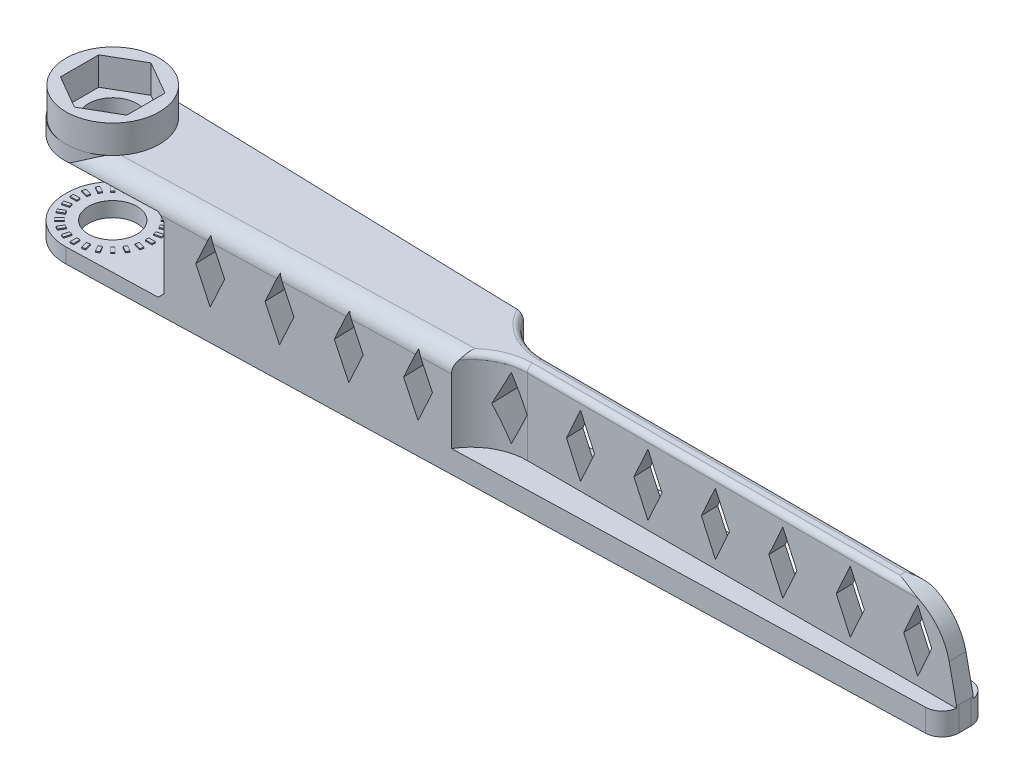
SolidWorks part; units mm, degrees
ref_plane "Front Plane" through (0, 0, 0) normal (0, 0, 1) x (1, 0, 0)
ref_plane "Top Plane" through (0, 0, 0) normal (0, 1, 0) x (1, 0, 0)
ref_plane "Right Plane" through (0, 0, 0) normal (1, 0, 0) x (0, 0, -1)
sketch "Sketch1" plane through (0, 0, 0) normal (0, 1, 0) x (1, 0, 0)
  line L0 (0, 8.2282) -> (0, 8.7718)
  line L1 (8.2249, 16.7687) -> (157.0843, 12.582)
  line L2 (160, 9.5832) -> (160, 7.4168)
  line L3 (157.0843, 4.418) -> (8.2249, 0.2313)
  line L4 (160, 8.5) -> (0, 8.5) construction
  arc A0 (160, 7.4168) -> (157.0843, 4.418) centre (157, 7.4168) cw
  arc A1 (157.0843, 12.582) -> (160, 9.5832) centre (157, 9.5832) cw
  arc A2 (8.2249, 0.2313) -> (0, 8.2282) centre (8, 8.2282) cw
  arc A3 (0, 8.7718) -> (8.2249, 16.7687) centre (8, 8.7718) cw
  point P7 (24.5016, 9.4444)
  point P8 (0, 8.5)
  point P9 (116.4876, 4.1839)
  point P12 (160, 4.5)
  point P15 (160, 12.5)
  point P18 (0, 0)
  point P21 (0, 17)
  dimension "D4" = 3
  dimension "D5" = 8
  dimension "D1" = 17
  dimension "D2" = 8
  dimension "D3" = 160
extrude "Boss-Extrude1" add sketch "Sketch1" along normal blind 18.5
sketch "Sketch2" plane through (0, 18.5, 0) normal (0, 1, 0) x (1, 0, 0)
  line L0 (75, 14.8906) -> (75, 10)
  line L1 (75, 7) -> (157, 7)
  line L2 (157, 7) -> (157, 10)
  line L3 (157, 10) -> (75, 10)
  line L4 (160, 7.4168) -> (160, 9.5832)
  line L5 (157.0843, 12.582) -> (8.2249, 16.7687)
  line L6 (0, 8.7718) -> (0, 8.2282)
  line L7 (8.2249, 0.2313) -> (157.0843, 4.418)
  line L8 (160, 7.4168) -> (160, 9.5832)
  line L9 (157.0843, 12.582) -> (75, 14.8906)
  line L11 (75, 2.1094) -> (157.0843, 4.418)
  line L12 (160, 8.5) -> (157, 8.5) construction
  line L15 (75, 7) -> (75, 2.1094)
  arc A4 (157.0843, 4.418) -> (160, 7.4168) centre (157, 7.4168) ccw
  arc A5 (160, 9.5832) -> (157.0843, 12.582) centre (157, 9.5832) ccw
  arc A6 (8.2249, 16.7687) -> (0, 8.7718) centre (8, 8.7718) ccw
  arc A7 (0, 8.2282) -> (8.2249, 0.2313) centre (8, 8.2282) ccw
  arc A8 (157.0843, 4.418) -> (160, 7.4168) centre (157, 7.4168) ccw
  arc A9 (160, 9.5832) -> (157.0843, 12.582) centre (157, 9.5832) ccw
  point P13 (0, 0)
  point P16 (75, 9.5832)
  dimension "D2" = 75
  dimension "D3" = 3
  dimension "D4" = 3
  dimension "D1" = 0
extrude "Cut-Extrude1" cut sketch "Sketch2" against normal offset from surface (14.5 mm away) 4 up to face at (81.0572, 0, -8.5)
chamfer "Chamfer1" distance 14.5 angle 12 1 edges at (157, 4, -8.5)
sketch "Sketch3" plane through (0, 0, 0) normal (0.0281, 0, 0.9996) x (0.9996, 0, -0.0281)
  line L0 (30.7282, 11) -> (33.2282, 16.5)
  line L1 (33.2282, 16.5) -> (35.7282, 11)
  line L2 (35.7282, 11) -> (33.2282, 5.5)
  line L3 (33.2282, 5.5) -> (30.7282, 11)
  line L4 (33.2282, 16.5) -> (33.2282, 5.5) construction
  line L5 (30.7282, 11) -> (35.7282, 11) construction
  line L6 (8.2282, 11) -> (33.2282, 11) construction
  line L7 (8.2282, 18.5) -> (8.2282, 0) construction
  line L8 (42.7282, 11) -> (45.2282, 16.5)
  line L9 (45.2282, 16.5) -> (47.7282, 11)
  line L10 (47.7282, 11) -> (45.2282, 5.5)
  line L11 (45.2282, 5.5) -> (42.7282, 11)
  line L12 (45.2282, 16.5) -> (45.2282, 5.5) construction
  line L13 (42.7282, 11) -> (47.7282, 11) construction
  line L14 (20.2282, 11) -> (45.2282, 11) construction
  line L15 (54.7282, 11) -> (57.2282, 16.5)
  line L16 (57.2282, 16.5) -> (59.7282, 11)
  line L17 (59.7282, 11) -> (57.2282, 5.5)
  line L18 (57.2282, 5.5) -> (54.7282, 11)
  line L19 (57.2282, 16.5) -> (57.2282, 5.5) construction
  line L20 (54.7282, 11) -> (59.7282, 11) construction
  line L21 (32.2282, 11) -> (57.2282, 11) construction
  line L22 (66.7282, 11) -> (69.2282, 16.5)
  line L23 (69.2282, 16.5) -> (71.7282, 11)
  line L24 (71.7282, 11) -> (69.2282, 5.5)
  line L25 (69.2282, 5.5) -> (66.7282, 11)
  line L26 (69.2282, 16.5) -> (69.2282, 5.5) construction
  line L27 (66.7282, 11) -> (71.7282, 11) construction
  line L28 (44.2282, 11) -> (69.2282, 11) construction
  line L29 (78.7282, 11) -> (81.2282, 16.5)
  line L30 (81.2282, 16.5) -> (83.7282, 11)
  line L31 (83.7282, 11) -> (81.2282, 5.5)
  line L32 (81.2282, 5.5) -> (78.7282, 11)
  line L33 (81.2282, 16.5) -> (81.2282, 5.5) construction
  line L34 (78.7282, 11) -> (83.7282, 11) construction
  line L35 (56.2282, 11) -> (81.2282, 11) construction
  line L36 (90.7282, 11) -> (93.2282, 16.5)
  line L37 (93.2282, 16.5) -> (95.7282, 11)
  line L38 (95.7282, 11) -> (93.2282, 5.5)
  line L39 (93.2282, 5.5) -> (90.7282, 11)
  line L40 (93.2282, 16.5) -> (93.2282, 5.5) construction
  line L41 (90.7282, 11) -> (95.7282, 11) construction
  line L42 (68.2282, 11) -> (93.2282, 11) construction
  line L43 (102.7282, 11) -> (105.2282, 16.5)
  line L44 (105.2282, 16.5) -> (107.7282, 11)
  line L45 (107.7282, 11) -> (105.2282, 5.5)
  line L46 (105.2282, 5.5) -> (102.7282, 11)
  line L47 (105.2282, 16.5) -> (105.2282, 5.5) construction
  line L48 (102.7282, 11) -> (107.7282, 11) construction
  line L49 (80.2282, 11) -> (105.2282, 11) construction
  line L50 (114.7282, 11) -> (117.2282, 16.5)
  line L51 (117.2282, 16.5) -> (119.7282, 11)
  line L52 (119.7282, 11) -> (117.2282, 5.5)
  line L53 (117.2282, 5.5) -> (114.7282, 11)
  line L54 (117.2282, 16.5) -> (117.2282, 5.5) construction
  line L55 (114.7282, 11) -> (119.7282, 11) construction
  line L56 (92.2282, 11) -> (117.2282, 11) construction
  line L57 (126.7282, 11) -> (129.2282, 16.5)
  line L58 (129.2282, 16.5) -> (131.7282, 11)
  line L59 (131.7282, 11) -> (129.2282, 5.5)
  line L60 (129.2282, 5.5) -> (126.7282, 11)
  line L61 (129.2282, 16.5) -> (129.2282, 5.5) construction
  line L62 (126.7282, 11) -> (131.7282, 11) construction
  line L63 (104.2282, 11) -> (129.2282, 11) construction
  line L64 (138.7282, 11) -> (141.2282, 16.5)
  line L65 (141.2282, 16.5) -> (143.7282, 11)
  line L66 (143.7282, 11) -> (141.2282, 5.5)
  line L67 (141.2282, 5.5) -> (138.7282, 11)
  line L68 (141.2282, 16.5) -> (141.2282, 5.5) construction
  line L69 (138.7282, 11) -> (143.7282, 11) construction
  line L70 (116.2282, 11) -> (141.2282, 11) construction
  line L71 (150.7282, 11) -> (153.2282, 16.5)
  line L72 (153.2282, 16.5) -> (155.7282, 11)
  line L73 (155.7282, 11) -> (153.2282, 5.5)
  line L74 (153.2282, 5.5) -> (150.7282, 11)
  line L75 (153.2282, 16.5) -> (153.2282, 5.5) construction
  line L76 (150.7282, 11) -> (155.7282, 11) construction
  line L77 (128.2282, 11) -> (153.2282, 11) construction
  line L85 (160.1045, 4) -> (75.1672, 4) construction
  point P8 (150.9703, 9.25)
  point P10 (0, 0)
  point P76 (125.0022, 11)
  point P77 (127.4812, 11)
  point P78 (159.2402, 11)
  point P79 (0, 0)
  dimension "D1" = 11
  dimension "D2" = 5
  dimension "D3" = 25
  dimension "D5" = 7
  dimension "D6" = 12
  dimension "D4" = 11
extrude "Cut-Extrude2" cut sketch "Sketch3" against normal through all
sketch "Sketch4" plane through (0, 18.5, 0) normal (0, 1, 0) x (1, 0, 0)
  line L0 (0, 8.7718) -> (0, 8.2282) construction
  line L1 (0, 8.5) -> (8.3, 8.5) construction
  circle A0 centre (8.3, 8.5) radius 8.3
  point P7 (0, 0)
  point P8 (0, 0)
  dimension "D1" = 16.6
extrude "Boss-Extrude2" add sketch "Sketch4" along normal blind 5
sketch "Sketch5" plane through (0, 23.5, 0) normal (0, 1, 0) x (1, 0, 0)
  line L0 (2.4, 11.9064) -> (8.3, 15.3127)
  line L1 (8.3, 15.3127) -> (14.2, 11.9064)
  line L2 (14.2, 11.9064) -> (14.2, 5.0936)
  line L3 (14.2, 5.0936) -> (8.3, 1.6873)
  line L4 (8.3, 1.6873) -> (2.4, 5.0936)
  line L5 (2.4, 5.0936) -> (2.4, 11.9064)
  line L6 (14.2, 8.5) -> (2.4, 8.5) construction
  line L7 (8.3, 15.3127) -> (8.3, 1.6873) construction
  point P4 (14.2, 8.5)
  point P9 (8.2386, 13.2957)
  point P10 (14.8952, 12.7807)
  point P11 (8.3, 18.685)
  point P12 (8.3, 1.778)
  point P13 (8.3, 8.5)
  dimension "D1" = 120
  dimension "D2" = 60
  dimension "D3" = 11.8
extrude "Cut-Extrude3" cut sketch "Sketch5" against normal up to surface (5 mm away) up to face at (79.989, 18.5, -8.5)
sketch "Sketch6" plane through (0, 0, 0) normal (0, -1, 0) x (1, 0, 0)
  circle A0 centre (8.3, -8.5) radius 4.3
  dimension "D1" = 8.6
extrude "Cut-Extrude4" cut sketch "Sketch6" against normal through all both and the other way through all
sketch "Sketch7" plane through (0, 0, 0) normal (0.0281, 0, 0.9996) x (0.9996, 0, -0.0281)
  line L0 (0.2282, 18.5) -> (0.2282, 0) construction
  line L1 (0.2282, 15.85) -> (25.2282, 15.85)
  line L2 (0.2282, 15.85) -> (0.2282, 2.65)
  line L3 (0.2282, 2.65) -> (25.2282, 2.65)
  line L4 (25.2282, 15.85) -> (25.2282, 2.65)
  point P6 (0.2282, 9.25)
  dimension "D1" = 13.2
  dimension "D2" = 25
extrude "Cut-Extrude5" cut sketch "Sketch7" against normal through all both
sketch "Sketch8" plane through (0, 15.85, 0) normal (0, -1, 0) x (1, 0, 0)
  circle A0 centre (8.3, -8.5) radius 4.3 construction
  circle A1 centre (8.3, -8.5) radius 4.3
  circle A2 centre (8.3, -8.5) radius 5.7
  dimension "D1" = 1.4
extrude "Boss-Extrude3" add sketch "Sketch8" along normal blind 2.4
sketch "Sketch9" plane through (0, 15.85, 0) normal (0, -1, 0) x (1, 0, 0)
  line L0 (8.3, -14.2) -> (8.3, -15.8) construction
  line L1 (8, -14.6) -> (8.6, -14.6)
  line L2 (8, -14.6) -> (8, -15.8)
  line L3 (8, -15.8) -> (8.6, -15.8)
  line L4 (8.6, -14.6) -> (8.6, -15.8)
  line L5 (6.4314, -14.3145) -> (6.1208, -15.4736)
  line L6 (6.4314, -14.3145) -> (7.011, -14.4698)
  line L7 (7.011, -14.4698) -> (6.7004, -15.6289)
  line L8 (6.1208, -15.4736) -> (6.7004, -15.6289)
  line L9 (4.9902, -13.6328) -> (4.3902, -14.672)
  line L10 (4.9902, -13.6328) -> (5.5098, -13.9328)
  line L11 (5.5098, -13.9328) -> (4.9098, -14.972)
  line L12 (4.3902, -14.672) -> (4.9098, -14.972)
  line L13 (3.7745, -12.6012) -> (2.926, -13.4497)
  line L14 (3.7745, -12.6012) -> (4.1988, -13.0255)
  line L15 (4.1988, -13.0255) -> (3.3503, -13.874)
  line L16 (2.926, -13.4497) -> (3.3503, -13.874)
  line L17 (2.8672, -11.2902) -> (1.828, -11.8902)
  line L18 (2.8672, -11.2902) -> (3.1672, -11.8098)
  line L19 (3.1672, -11.8098) -> (2.128, -12.4098)
  line L20 (1.828, -11.8902) -> (2.128, -12.4098)
  line L21 (2.3302, -9.789) -> (1.1711, -10.0996)
  line L22 (2.3302, -9.789) -> (2.4855, -10.3686)
  line L23 (2.4855, -10.3686) -> (1.3264, -10.6792)
  line L24 (1.1711, -10.0996) -> (1.3264, -10.6792)
  line L25 (2.2, -8.2) -> (1, -8.2)
  line L26 (2.2, -8.2) -> (2.2, -8.8)
  line L27 (2.2, -8.8) -> (1, -8.8)
  line L28 (1, -8.2) -> (1, -8.8)
  line L29 (2.4855, -6.6314) -> (1.3264, -6.3208)
  line L30 (2.4855, -6.6314) -> (2.3302, -7.211)
  line L31 (2.3302, -7.211) -> (1.1711, -6.9004)
  line L32 (1.3264, -6.3208) -> (1.1711, -6.9004)
  line L33 (3.1672, -5.1902) -> (2.128, -4.5902)
  line L34 (3.1672, -5.1902) -> (2.8672, -5.7098)
  line L35 (2.8672, -5.7098) -> (1.828, -5.1098)
  line L36 (2.128, -4.5902) -> (1.828, -5.1098)
  line L37 (4.1988, -3.9745) -> (3.3503, -3.126)
  line L38 (4.1988, -3.9745) -> (3.7745, -4.3988)
  line L39 (3.7745, -4.3988) -> (2.926, -3.5503)
  line L40 (3.3503, -3.126) -> (2.926, -3.5503)
  line L41 (5.5098, -3.0672) -> (4.9098, -2.028)
  line L42 (5.5098, -3.0672) -> (4.9902, -3.3672)
  line L43 (4.9902, -3.3672) -> (4.3902, -2.328)
  line L44 (4.9098, -2.028) -> (4.3902, -2.328)
  line L45 (7.011, -2.5302) -> (6.7004, -1.3711)
  line L46 (7.011, -2.5302) -> (6.4314, -2.6855)
  line L47 (6.4314, -2.6855) -> (6.1208, -1.5264)
  line L48 (6.7004, -1.3711) -> (6.1208, -1.5264)
  line L49 (8.6, -2.4) -> (8.6, -1.2)
  line L50 (8.6, -2.4) -> (8, -2.4)
  line L51 (8, -2.4) -> (8, -1.2)
  line L52 (8.6, -1.2) -> (8, -1.2)
  line L53 (10.1686, -2.6855) -> (10.4792, -1.5264)
  line L54 (10.1686, -2.6855) -> (9.589, -2.5302)
  line L55 (9.589, -2.5302) -> (9.8996, -1.3711)
  line L56 (10.4792, -1.5264) -> (9.8996, -1.3711)
  line L57 (11.6098, -3.3672) -> (12.2098, -2.328)
  line L58 (11.6098, -3.3672) -> (11.0902, -3.0672)
  line L59 (11.0902, -3.0672) -> (11.6902, -2.028)
  line L60 (12.2098, -2.328) -> (11.6902, -2.028)
  line L61 (12.8255, -4.3988) -> (13.674, -3.5503)
  line L62 (12.8255, -4.3988) -> (12.4012, -3.9745)
  line L63 (12.4012, -3.9745) -> (13.2497, -3.126)
  line L64 (13.674, -3.5503) -> (13.2497, -3.126)
  line L65 (13.7328, -5.7098) -> (14.772, -5.1098)
  line L66 (13.7328, -5.7098) -> (13.4328, -5.1902)
  line L67 (13.4328, -5.1902) -> (14.472, -4.5902)
  line L68 (14.772, -5.1098) -> (14.472, -4.5902)
  line L69 (14.2698, -7.211) -> (15.4289, -6.9004)
  line L70 (14.2698, -7.211) -> (14.1145, -6.6314)
  line L71 (14.1145, -6.6314) -> (15.2736, -6.3208)
  line L72 (15.4289, -6.9004) -> (15.2736, -6.3208)
  line L73 (14.4, -8.8) -> (15.6, -8.8)
  line L74 (14.4, -8.8) -> (14.4, -8.2)
  line L75 (14.4, -8.2) -> (15.6, -8.2)
  line L76 (15.6, -8.8) -> (15.6, -8.2)
  line L77 (14.1145, -10.3686) -> (15.2736, -10.6792)
  line L78 (14.1145, -10.3686) -> (14.2698, -9.789)
  line L79 (14.2698, -9.789) -> (15.4289, -10.0996)
  line L80 (15.2736, -10.6792) -> (15.4289, -10.0996)
  line L81 (13.4328, -11.8098) -> (14.472, -12.4098)
  line L82 (13.4328, -11.8098) -> (13.7328, -11.2902)
  line L83 (13.7328, -11.2902) -> (14.772, -11.8902)
  line L84 (14.472, -12.4098) -> (14.772, -11.8902)
  line L85 (12.4012, -13.0255) -> (13.2497, -13.874)
  line L86 (12.4012, -13.0255) -> (12.8255, -12.6012)
  line L87 (12.8255, -12.6012) -> (13.674, -13.4497)
  line L88 (13.2497, -13.874) -> (13.674, -13.4497)
  line L89 (11.0902, -13.9328) -> (11.6902, -14.972)
  line L90 (11.0902, -13.9328) -> (11.6098, -13.6328)
  line L91 (11.6098, -13.6328) -> (12.2098, -14.672)
  line L92 (11.6902, -14.972) -> (12.2098, -14.672)
  line L93 (9.589, -14.4698) -> (9.8996, -15.6289)
  line L94 (9.589, -14.4698) -> (10.1686, -14.3145)
  line L95 (10.1686, -14.3145) -> (10.4792, -15.4736)
  line L96 (9.8996, -15.6289) -> (10.4792, -15.4736)
  circle A0 centre (8.3, -8.5) radius 5.7 construction
  point P104 (8.3, -8.5)
  dimension "D1" = 0.6
  dimension "D2" = 1.2
  dimension "D3" = 1.6
  dimension "D4" = 24
extrude "Boss-Extrude4" add sketch "Sketch9" along normal blind 0.2
ref_plane "Plane1" through (0, 9.25, 0) normal (0, 1, 0) x (1, 0, 0)
mirror "Mirror1" about plane through (0, 9.25, 0) normal (0, 1, 0) of "Boss-Extrude4"
fillet "Fillet1" radius 10 3 edges at (157, 18.5, -8.5) (75, 11.25, -10) (75, 11.25, -7)
fillet "Fillet2" radius 3 1 edges at (42.1559, 18.5, -1.1856)
fillet "Fillet3" radius 1 4 edges at (116.2492, 18.5, -10) (78.6512, 18.5, -11.3082) (80.5887, 18.5, -6.537) (116.2492, 18.5, -7)
chamfer "Chamfer2" distance 1 angle 45 2 edges at (24.9989, 2.65, -8.5062) (24.9986, 15.85, -8.5164)
